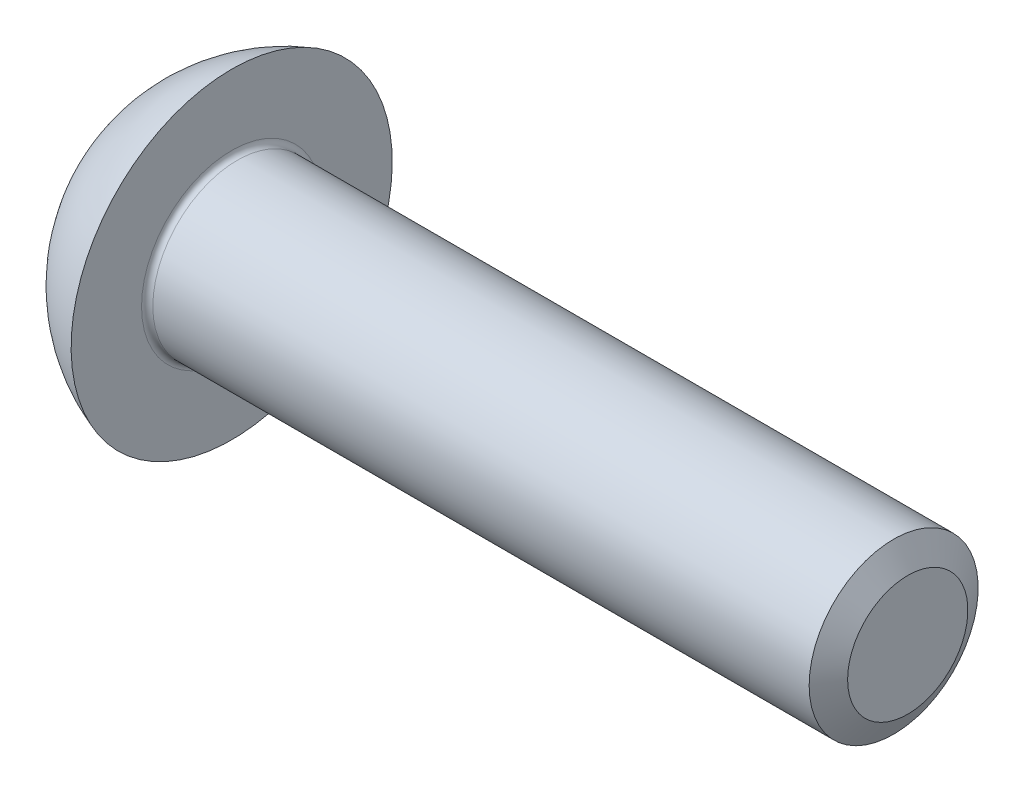
SolidWorks part; units mm, degrees
ref_plane "前视基准面" through (0, 0, 0) normal (0, 0, 1) x (1, 0, 0)
ref_plane "上视基准面" through (0, 0, 0) normal (0, 1, 0) x (1, 0, 0)
ref_plane "右视基准面" through (0, 0, 0) normal (1, 0, 0) x (0, 0, -1)
sketch "尺寸草图" plane through (0, 0, 0) normal (0, 0, 1) x (1, 0, 0)
  line L0 (0, 0) -> (12, 0) construction
  line L1 (12, 0) -> (12, 1.5) construction
  line L2 (12, 1.5) -> (11.5, 1.5) construction
  line L3 (0, 0) -> (0, 2.85) construction
  point P3 (1, 0)
  point P6 (12, 1.8)
  point P7 (0, 0.55)
  point P9 (1.65, 0)
  point P10 (1.75, 0)
  point P11 (12, 1)
  point P12 (2.79, 0)
  point P13 (2.99, 0)
  point P14 (12, 3.7113)
  dimension "r" = 0.1
  dimension "d" = 3
  dimension "dk" = 5.7
  dimension "l" = 12
  dimension "P" = 0.5
  dimension "a" = 1
  dimension "da" = 3.6
  dimension "e" = 2.3
  dimension "K" = 1.65
  dimension "s" = 2
  dimension "t" = 1.04
  dimension "w" = 0.2
  dimension "zslwx" = 1.9113
sketch "草图1" plane through (0, 0, 0) normal (0, 0, 1) x (1, 0, 0)
  line L0 (-13.65, 0) -> (0, 0) construction
  line L1 (0, 1.5) -> (-11.9, 1.5)
  line L2 (-12, 1.6) -> (-12, 2.85)
  line L3 (-13.65, 0) -> (-13.65, 1.5)
  line L4 (0, 1.5) -> (0, 0)
  line L5 (-13.65, 0) -> (0, 0)
  arc A0 (-12, 2.85) -> (-13.65, 1.5) centre (-11.0455, 0) ccw
  arc A1 (-11.9, 1.5) -> (-12, 1.6) centre (-11.9, 1.6) cw
  point P10 (-12, 1.5)
  dimension "r" = 0.1
  dimension "d" = 3
  dimension "dk" = 5.7
  dimension "k" = 1.65
  dimension "l" = 12
revolve "旋转1" add sketch "草图1" angle 360 about L0
cosmetic thread "装饰螺纹线1" parameters "D1"=1.9113, "D2"=2.58
sketch "草图2" plane through (-13.65, 0, 0) normal (-1, 0, 0) x (0, 0, 1)
  line L1 (0, 1.1547) -> (-1, 0.5774)
  line L2 (-1, 0.5774) -> (-1, -0.5774)
  line L3 (-1, -0.5774) -> (0, -1.1547)
  line L4 (0, -1.1547) -> (1, -0.5774)
  line L5 (1, -0.5774) -> (1, 0.5774)
  line L6 (1, 0.5774) -> (0, 1.1547)
  circle A0 centre (0, 0) radius 1 construction
  dimension "s" = 2
extrude "切除-拉伸1" cut sketch "草图2" against normal blind 1.65
sketch "草图6" plane through (0, 0, 0) normal (0, 0, 1) x (1, 0, 0)
  line L0 (-12.61, 1.1547) -> (-12, 0)
  line L1 (-11.7, 1.1547) -> (-11.7, 0)
  line L2 (-11.7, 1.1547) -> (-12.61, 1.1547)
  line L3 (-13.65, 0) -> (-12, 0) construction
  line L4 (-11.7, 0) -> (-12, 0)
  line L5 (-13.65, 0) -> (-15.95, 0) construction
  dimension "k" = 1.65
  dimension "e" = 2.3
  dimension "t" = 1.04
  dimension "e-s" = 0.3
revolve "旋转2" add sketch "草图6" angle 360 about L3
sketch "草图7" plane through (0, 0, 0) normal (0, 0, 1) x (1, 0, 0)
  line L3 (-13.65, 1.1547) -> (-13.35, 0)
  line L4 (-13.65, 0) -> (-13.35, 0) construction
  line L7 (-13.65, 1.1547) -> (-13.65, 0)
  line L8 (-13.65, 0) -> (-13.35, 0)
  dimension "e-s" = 0.3
revolve "切除-旋转5" cut sketch "草图7" angle 360 about L4
sketch "草图4" plane through (0, 0, 0) normal (0, 0, 1) x (1, 0, 0)
  line L0 (-0.25, 1.5) -> (0, 1.067)
  line L1 (-0.25, 1.5) -> (0.25, 1.5)
  line L2 (0.25, 1.5) -> (0, 1.067)
  line L4 (0, -1.5) -> (0, 1.5) construction
  line L5 (-0.25, 0) -> (0.25, 0) construction
  dimension "d" = 1.5
  dimension "p" = 0.5
revolve "切除-旋转1" cut sketch "草图4" angle 360 about L5
ref_axis "基准轴1" through (-8.1887, 0, 0) along (1, 0, 0)
pattern_linear "阵列(线性)1" [suppressed] count 22 spacing 0.5 along (-1, 0, 0) of bodies 104
equation "\"d@草图1\"=\"d@尺寸草图\""
equation "\"l@草图1\"=\"l@尺寸草图\""
equation "\"dk@草图1\"=\"dk@尺寸草图\""
equation "\"k@草图1\"=\"K@尺寸草图\""
equation "\"r@草图1\"=\"r@尺寸草图\""
equation "\"s@草图2\"=\"s@尺寸草图\""
equation "\"t@草图6\"=\"t@尺寸草图\""
equation "\"e@草图6\"=\"e@尺寸草图\""
equation "\"p@草图4\"=\"P@尺寸草图\""
equation "\"D2@装饰螺纹线1\" = \"d@草图1\" * 0.86"
equation "\"k@切除-拉伸1\" = \"k@草图1\""
equation "\"k@草图6\" = \"k@切除-拉伸1\""
equation "\"e-s@草图6\" = \"e@草图6\" - \"s@草图2\""
equation "\"e-s@草图7\" = \"e-s@草图6\""
equation "\"d@草图4\" = \"d@草图1\" / 2"
equation "\"D3@阵列(线性)1\"=\"P@尺寸草图\""
equation "\"D1@阵列(线性)1\"=(\"l@尺寸草图\"-\"a@尺寸草图\")/\"P@尺寸草图\""
equation "\"D1@装饰螺纹线1\"=\"zslwx@尺寸草图\""
